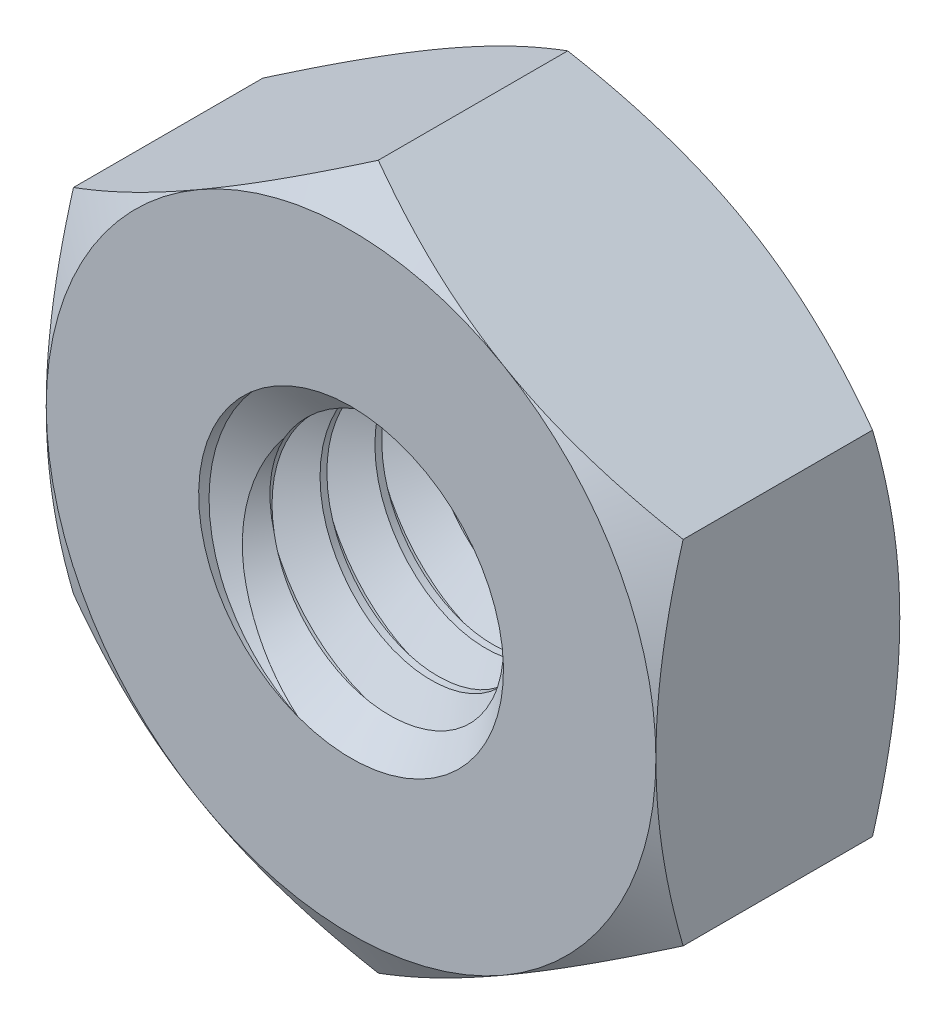
SolidWorks part; units mm, degrees
ref_plane "Front" through (0, 0, 0) normal (0, 0, 1) x (1, 0, 0)
ref_plane "Top" through (0, 0, 0) normal (0, 1, 0) x (1, 0, 0)
ref_plane "Right" through (0, 0, 0) normal (1, 0, 0) x (0, 0, -1)
sketch "Sketch1" plane through (0, 0, 0) normal (0, 0, 1) x (1, 0, 0)
  line L1 (-2.5, 1.4434) -> (-2.5, -1.4434)
  line L2 (-2.5, -1.4434) -> (0, -2.8868)
  line L3 (0, -2.8868) -> (2.5, -1.4434)
  line L4 (2.5, -1.4434) -> (2.5, 1.4434)
  line L5 (2.5, 1.4434) -> (0, 2.8868)
  line L6 (0, 2.8868) -> (-2.5, 1.4434)
  circle A0 centre (0, 0) radius 2.5 construction
  circle A1 centre (0, 0) radius 1.25 construction
  point P10 (0, 1.25)
  dimension "hex" = 5
  dimension "dia" = 2.5
extrude "Extrude1" add sketch "Sketch1" along normal mid plane 2
sketch "Sketch4" plane through (0, 0, -1) normal (0, 0, -1) x (-1, 0, 0)
  circle A0 centre (0, 0) radius 1.25 construction
  circle A1 centre (0, 0) radius 1.25
sketch "Sketch10" plane through (0, 0, 1) normal (0, 0, 1) x (1, 0, 0)
  circle A0 centre (0, 0) radius 1.25 construction
  circle A1 centre (0, 0) radius 1.25
extrude "Cut-Extrude2" cut sketch "Sketch10" against normal through all draft 45
sketch "Sketch11" plane through (0, 0, -1) normal (0, 0, -1) x (-1, 0, 0)
  circle A0 centre (0, 0) radius 1.25 construction
  circle A1 centre (0, 0) radius 1.25
extrude "Cut-Extrude3" cut sketch "Sketch11" against normal through all draft 45
sketch "Sketch13" plane through (0, 0, -1) normal (0, 0, -1) x (-1, 0, 0)
  circle A0 centre (0, 0) radius 1.25 construction
  circle A1 centre (0, 0) radius 1.25
extrude "Boss-Extrude1" add sketch "Sketch13" against normal up to vertex (2 mm away) separate body up to point (-2.5, 1.4434, 1)
curve "Helix/Spiral3" pitch 0.45 height 2 turns 4.4444
sketch "Sketch12" plane through (0, 0, 0) normal (1, 0, 0) x (0, 0, -1)
  line L0 (1.3938, 1.25) -> (1, 1.25)
  line L1 (1.3938, 1.25) -> (1.225, 0.9577)
  line L2 (1.225, 0.9577) -> (1.1688, 0.9577)
  line L3 (1.1688, 0.9577) -> (1, 1.25)
  line L4 (1.1969, 0.9577) -> (1.1969, 1.25) construction
  line L5 (1.0844, 1.1039) -> (1.3094, 1.1039) construction
  dimension "D1" = 60
  dimension "D2" = 0.0563
  dimension "D3" = 0.225
sweep "Cut-Sweep1" cut profiles "Sketch12" path "Helix/Spiral3"
combine bodies "Combine1" operation type subtract main body 116 bodies to subtract 118
sketch "Sketch7" plane through (0, 0, 1) normal (0, 0, 1) x (1, 0, 0)
  circle A0 centre (0, 0) radius 2.5 construction
  circle A1 centre (0, 0) radius 2.5
extrude "Extrude2" cut sketch "Sketch7" against normal blind 25.4 draft 60 flip side to cut
mirror "Mirror2" about plane through (0, 0, 0) normal (0, 0, 1) of "Extrude2"
equation "\"D3@Helix/Spiral3\" = \"length@Extrude1\" "
equation "\"D2@Sketch12\" = \"D4@Helix/Spiral3\"*.125"
equation "\"D3@Sketch12\" = \"D4@Helix/Spiral3\"*.50"
